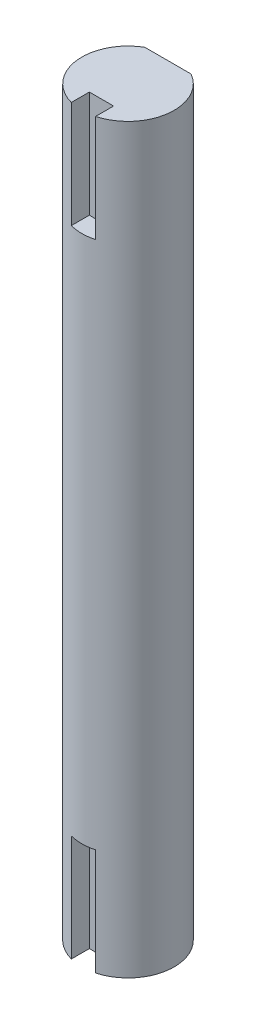
SolidWorks part; units mm, degrees
material "AISI 1045 Steel, cold drawn"
ref_plane "X-Y Datum" through (0, 0, 0) normal (0, 0, 1) x (1, 0, 0)
ref_plane "X-Z Datum" through (0, 0, 0) normal (0, 1, 0) x (1, 0, 0)
ref_plane "Y-Z Datum" through (0, 0, 0) normal (1, 0, 0) x (0, 0, -1)
sketch "Sketch1" plane through (0, 0, 0) normal (0, 1, 0) x (1, 0, 0)
  line L0 (-2.3876, 4.1208) -> (2.3876, 4.1208)
  circle A0 centre (0, 0) radius 4.7625
  dimension "D1" = 9.525
  dimension "D2" = 4.7752
extrude "Boss-Extrude1" add sketch "Sketch1" along normal blind 38.25 and the other way blind 38.25 contours L0 A0 region at (0, 0, 0.1312)
sketch "Sketch2" plane through (0, -38.25, 0) normal (0, -1, 0) x (1, 0, 0)
  line L0 (-1.25, 4.5955) -> (-1.25, 2.7375)
  line L1 (-1.25, 2.7375) -> (1.25, 2.7375)
  line L2 (1.25, 2.7375) -> (1.25, 4.5955)
  arc A0 (2.3876, -4.1208) -> (-2.3876, -4.1208) centre (0, 0) ccw construction
  circle A1 centre (0, 0) radius 4.7625 construction
  point P5 (0, -4.7625)
  point P8 (0, 2.7375)
  dimension "D1" = 2.5
  dimension "D2" = 7.5
extrude "Cut-Extrude1" cut sketch "Sketch2" against normal blind 11 and the other way through all
sketch "Sketch3" plane through (0, 38.25, 0) normal (0, 1, 0) x (1, 0, 0)
  line L0 (-1.25, -4.5955) -> (-1.25, -2.7375)
  line L1 (-1.25, -2.7375) -> (1.25, -2.7375)
  line L2 (1.25, -2.7375) -> (1.25, -4.5955)
  circle A0 centre (0, 0) radius 4.7625 construction
  arc A1 (-1.25, -4.5955) -> (1.25, -4.5955) centre (0, 0) ccw
  point P6 (0, -2.7375)
  point P9 (0, 4.7625)
  dimension "D1" = 2.5
  dimension "D2" = 7.5
extrude "Cut-Extrude2" cut sketch "Sketch3" against normal blind 11
